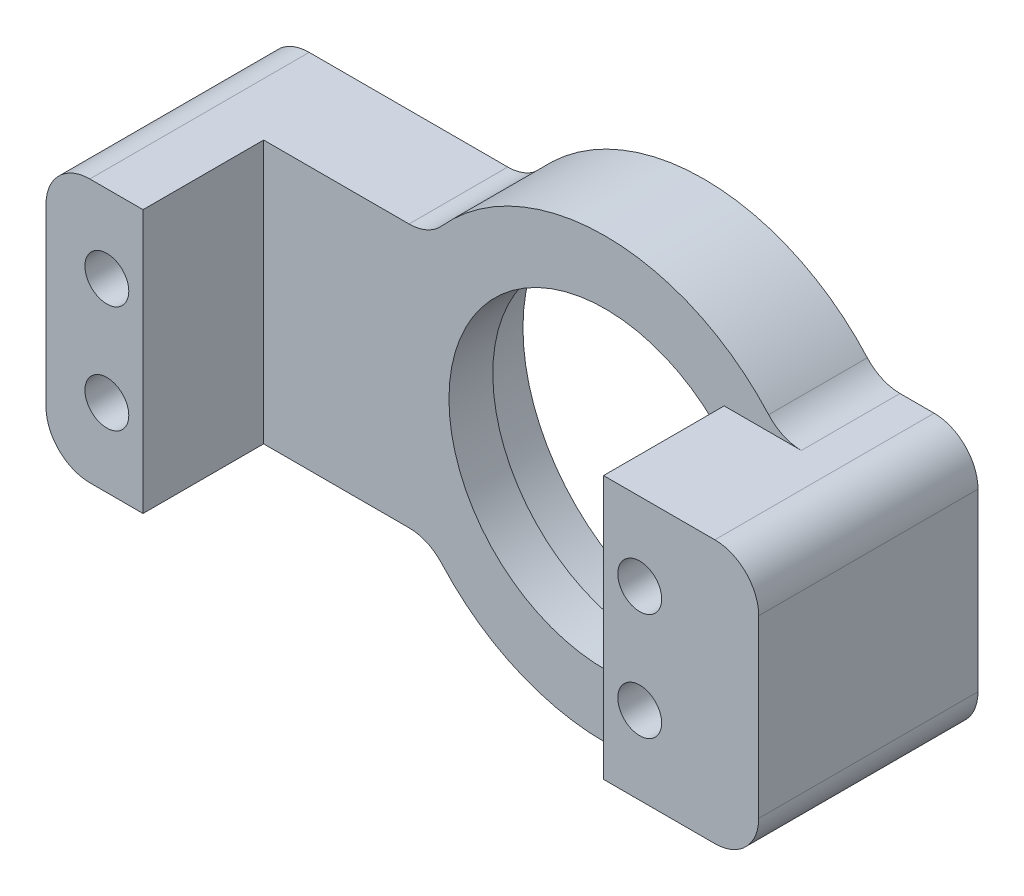
SolidWorks part; units mm, degrees
ref_plane "Front Plane" through (0, 0, 0) normal (0, 0, 1) x (1, 0, 0)
ref_plane "Top Plane" through (0, 0, 0) normal (0, 1, 0) x (1, 0, 0)
ref_plane "Right Plane" through (0, 0, 0) normal (1, 0, 0) x (0, 0, -1)
sketch "Sketch1" plane through (0, 0, 0) normal (0, 0, 1) x (1, 0, 0)
  line L0 (0, 113.0073) -> (17, 113.0073) construction
  line L1 (-40, 125.0073) -> (-16, 125.0073)
  line L2 (-40, 125.0073) -> (-40, 101.0073)
  line L3 (-40, 101.0073) -> (-16, 101.0073)
  line L4 (25, 125.0073) -> (25, 101.0073)
  line L6 (16, 125.0073) -> (25, 125.0073)
  line L8 (16, 101.0073) -> (25, 101.0073)
  arc A0 (16, 125.0073) -> (-16, 125.0073) centre (0, 113.0073) ccw
  circle A1 centre (0, 113.0073) radius 16.5
  arc A2 (-16, 101.0073) -> (16, 101.0073) centre (0, 113.0073) ccw
  dimension "D1" = 12
  dimension "D3" = 25
  dimension "D4" = 40
extrude "Boss-Extrude1" add sketch "Sketch1" along normal blind 5
sketch "Sketch2" plane through (0, 0, 5) normal (0, 0, 1) x (1, 0, 0)
  line L6 (-16, 125.0073) -> (-40, 125.0073)
  line L7 (-40, 125.0073) -> (-40, 101.0073)
  line L8 (-40, 101.0073) -> (-16, 101.0073)
  line L9 (16, 101.0073) -> (25, 101.0073)
  line L10 (25, 101.0073) -> (25, 125.0073)
  line L11 (25, 125.0073) -> (16, 125.0073)
  line L12 (-16, 125.0073) -> (-40, 125.0073)
  line L13 (-40, 125.0073) -> (-40, 101.0073)
  line L14 (-40, 101.0073) -> (-16, 101.0073)
  line L15 (16, 101.0073) -> (25, 101.0073)
  line L16 (25, 101.0073) -> (25, 125.0073)
  line L17 (25, 125.0073) -> (16, 125.0073)
  circle A0 centre (0, 113.0073) radius 14.25
  arc A2 (-16, 101.0073) -> (16, 101.0073) centre (0, 113.0073) ccw
  arc A3 (16, 125.0073) -> (-16, 125.0073) centre (0, 113.0073) ccw
  arc A4 (-16, 101.0073) -> (16, 101.0073) centre (0, 113.0073) ccw
  arc A5 (16, 125.0073) -> (-16, 125.0073) centre (0, 113.0073) ccw
  dimension "D1" = 0
extrude "Boss-Extrude2" add sketch "Sketch2" along normal blind 4
sketch "Sketch4" plane through (0, 0, 9) normal (0, 0, 1) x (1, 0, 0)
  line L0 (-40, 101.0073) -> (-16, 101.0073) construction
  line L1 (25, 101.0073) -> (10.85, 101.0073)
  line L2 (25, 101.0073) -> (25, 125.0073)
  line L3 (25, 125.0073) -> (10.85, 125.0073)
  line L4 (10.85, 101.0073) -> (10.85, 125.0073)
  line L5 (-40, 125.0073) -> (-31.15, 125.0073)
  line L6 (-40, 125.0073) -> (-40, 101.0073)
  line L7 (-40, 101.0073) -> (-31.15, 101.0073)
  line L8 (-31.15, 125.0073) -> (-31.15, 101.0073)
  line L9 (-30.15, 103.0073) -> (-30.15, 123.0073) construction
  line L10 (9.85, 123.0073) -> (9.85, 103.0073) construction
  line L11 (25, 125.0073) -> (16, 125.0073) construction
  point P16 (25, 125.0073)
  dimension "D1" = 1
  dimension "D2" = 1
extrude "Boss-Extrude4" add sketch "Sketch4" along normal blind 11
fillet "Fillet1" radius 4 8 edges at (16, 125.0073, 4.5) (-16, 125.0073, 4.5) (-16, 101.0073, 4.5) (16, 101.0073, 4.5) (-40, 101.0073, 10) (-40, 125.0073, 10) (25, 125.0073, 10) (25, 101.0073, 10)
sketch "Sketch5" plane through (0, 0, 20) normal (0, 0, 1) x (1, 0, 0)
  circle A0 centre (-34.45, 108.1073) radius 2
  circle A1 centre (-34.45, 117.9073) radius 2
  circle A2 centre (14.15, 108.1073) radius 2
  circle A3 centre (14.15, 117.9073) radius 2
extrude "Cut-Extrude1" cut sketch "Sketch5" against normal blind 4
